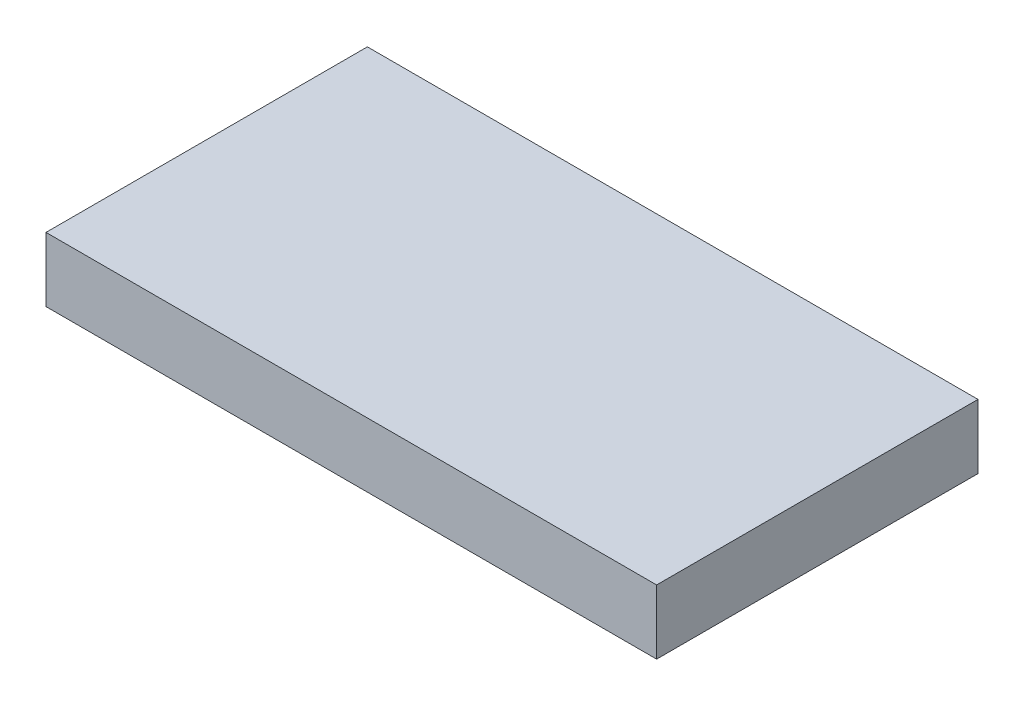
SolidWorks part; units mm, degrees
ref_plane "Front Plane" through (0, 0, 0) normal (0, 0, 1) x (1, 0, 0)
ref_plane "Top Plane" through (0, 0, 0) normal (0, 1, 0) x (1, 0, 0)
ref_plane "Right Plane" through (0, 0, 0) normal (1, 0, 0) x (0, 0, -1)
sketch "Sketch1" plane through (0, 0, 0) normal (0, 1, 0) x (1, 0, 0)
  line L1 (-12.065, 6.35) -> (12.065, 6.35)
  line L2 (-12.065, 6.35) -> (-12.065, -6.35)
  line L3 (-12.065, -6.35) -> (12.065, -6.35)
  line L4 (12.065, 6.35) -> (12.065, -6.35)
  line L5 (-12.065, 6.35) -> (12.065, -6.35) construction
  line L6 (-12.065, -6.35) -> (12.065, 6.35) construction
  point P4 (0, 0)
  dimension "D1" = 24.13
  dimension "D2" = 12.7
extrude "Boss-Extrude1" add sketch "Sketch1" along normal blind 2.54
